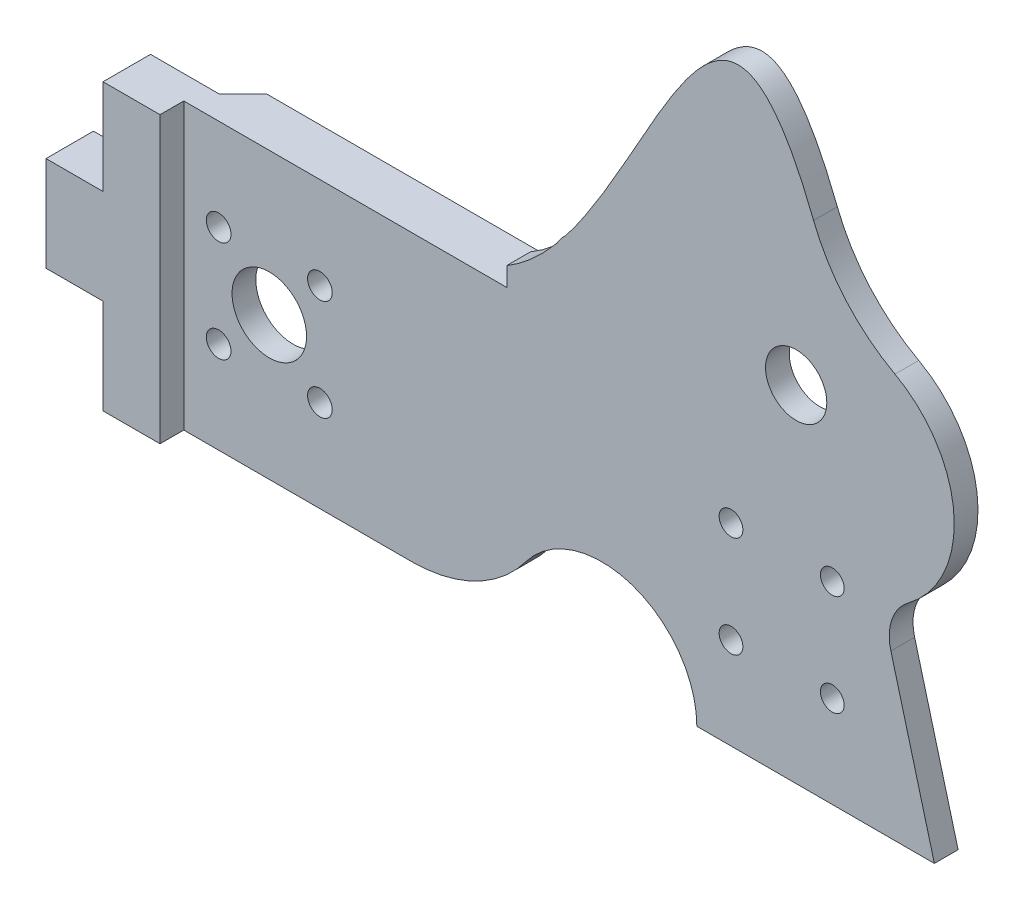
SolidWorks part; units mm, degrees
ref_plane "Front Plane" through (0, 0, 0) normal (0, 0, 1) x (1, 0, 0)
ref_plane "Top Plane" through (0, 0, 0) normal (0, 1, 0) x (1, 0, 0)
ref_plane "Right Plane" through (0, 0, 0) normal (1, 0, 0) x (0, 0, -1)
sketch "Sketch1" plane through (0, 0, 0) normal (0, 0, 1) x (1, 0, 0)
  line L0 (0, 0) -> (107.95, 0)
  line L3 (0, 38.1) -> (0, 25.4)
  line L4 (95.3675, 55.88) -> (0, 38.1)
  line L5 (0, 19.05) -> (100.2273, 19.05) construction
  line L6 (19.05, 19.05) -> (19.05, 28.62) construction
  line L7 (19.05, 19.05) -> (25.817, 25.817) construction
  line L8 (107.95, 0) -> (100.9363, 26.1756)
  line L10 (0, 12.7) -> (0, 0)
  line L11 (0, 25.4) -> (-7.62, 25.4)
  line L13 (0, 12.7) -> (-7.62, 12.7)
  line L14 (-7.62, 25.4) -> (-7.62, 12.7)
  line L15 (100.9363, 26.1756) -> (100.8688, 26.4276)
  arc A0 (100.8688, 26.4276) -> (95.3675, 55.88) centre (95.3675, 40.64) ccw
  circle A1 centre (95.3675, 40.64) radius 4.0957 construction
  circle A2 centre (19.05, 19.05) radius 9.57 construction
  circle A3 centre (25.817, 25.817) radius 1.651
  circle A4 centre (25.817, 12.283) radius 1.651
  circle A5 centre (12.283, 12.283) radius 1.651
  circle A6 centre (12.283, 25.817) radius 1.651
  point P26 (19.05, 19.05)
  dimension "D1" = 8.1915
  dimension "D5" = 15.24
  dimension "D4" = 19.14
  dimension "D7" = 3.302
  dimension "D11" = 97.0107
  dimension "D2" = 38.1
  dimension "D3" = 40.64
  dimension "D6" = 107.95
  dimension "D8" = 45
  dimension "D9" = 4
  dimension "D10" = 19.05
  dimension "D12" = 75
  dimension "D14" = 12.7
  dimension "D15" = 12.7
  dimension "D16" = 7.62
extrude "Boss-Extrude1" add sketch "Sketch1" along normal blind 3.175
sketch "Sketch2" plane through (0, 0, 3.175) normal (0, 0, 1) x (1, 0, 0)
  circle A0 centre (95.3675, 40.64) radius 38.1 construction
sketch "Sketch6" plane through (0, 0, 3.175) normal (0, 0, 1) x (1, 0, 0)
  line L0 (0, 0) -> (107.95, 0) construction
  line L1 (50.8, 0) -> (76.2, 0)
  arc A0 (76.2, 0) -> (50.8, 0) centre (63.5, 0) ccw
  dimension "D1" = 25.4
  dimension "D2" = 31.75
extrude "Cut-Extrude2" cut sketch "Sketch6" against normal blind 6.35
sketch "Sketch7" plane through (0, 0, 3.175) normal (0, 0, 1) x (1, 0, 0)
  line L0 (12.283, 25.817) -> (25.817, 12.283) construction
  line L1 (12.283, 12.283) -> (25.817, 25.817) construction
  line L2 (12.283, 25.817) -> (78.4839, 25.817) construction
  line L3 (11.7326, 12.283) -> (12.283, 12.283) construction
  circle A0 centre (19.05, 19.05) radius 4.9784
  circle A4 centre (80.7666, 12.283) radius 1.5875
  circle A5 centre (94.2997, 12.283) radius 1.5875
  circle A6 centre (80.7666, 25.817) radius 1.5875
  circle A7 centre (94.2997, 25.817) radius 1.5875
  dimension "D1" = 9.9568
  dimension "D2" = 3.175
  dimension "D3" = 13.5331
extrude "Cut-Extrude3" cut sketch "Sketch7" against normal through all
fillet "Fillet1" radius 6.35 1 edges at (100.8688, 26.4276, 1.5875)
sketch "Sketch8" plane through (0, 0, 3.175) normal (0, 0, 1) x (1, 0, 0)
  line L1 (0, 38.1) -> (50.8, 38.1)
  line L2 (0, 38.1) -> (0, 50.8)
  line L3 (0, 50.8) -> (50.8, 50.8)
  line L4 (50.8, 38.1) -> (50.8, 50.8)
  dimension "D1" = 50.8
  dimension "D2" = 12.7
extrude "Cut-Extrude4" cut sketch "Sketch8" against normal blind 50.8
sketch "Sketch9" plane through (0, 0, 3.175) normal (0, 0, 1) x (1, 0, 0)
  line L3 (50.8, 40.64) -> (57.15, 40.64)
  line L5 (57.15, 40.64) -> (50.8, 40.64)
  line L6 (57.15, 40.64) -> (57.15, 50.8)
  line L7 (57.15, 50.8) -> (50.8, 50.8)
  line L8 (50.8, 40.64) -> (50.8, 50.8)
  line L9 (0, 38.1) -> (50.8, 38.1) construction
  line M8 (50.8, 47.571) -> (50.8, 38.1)
  line M21 (95.3675, 55.88) -> (50.8, 47.571)
  dimension "D1" = 10.16
  dimension "D2" = 2.54
  dimension "D3" = 6.35
extrude "Cut-Extrude5" cut sketch "Sketch9" against normal blind 19.304 contours L3 L6 M21 M8 region at (54.0583, 44.4092, 3.175)
fillet "Fillet6" radius 6.35 1 edges at (57.15, 40.64, 1.5875)
fillet "Fillet7" radius 6.35 1 edges at (57.15, 48.7549, 1.5875)
fillet "Fillet8" radius 19.05 1 edges at (50.8, 0, 1.5875)
sketch "Sketch12" plane through (0, 0, 3.175) normal (0, 0, 1) x (1, 0, 0)
  line L0 (107.95, 0) -> (146.812, 0) construction
  line L1 (8.0257, 45.4128) -> (80.6683, 75.7903) construction
  line L2 (95.3675, 40.64) -> (80.6683, 75.7903) construction
  line L3 (80.6683, 75.7903) -> (79.4434, 78.7195) construction
  line L4 (50.8, 40.64) -> (85.0271, 40.64)
  line L5 (85.0271, 40.64) -> (95.3675, 55.88)
  arc A0 (61.8128, 49.6242) -> (56.8883, 45.1859) centre (62.9766, 43.3817) ccw construction
  circle A1 centre (19.05, 19.05) radius 28.575 construction
  circle A2 centre (95.3675, 40.64) radius 38.1 construction
  circle A3 centre (80.6683, 75.7903) radius 3.175 construction
  spline S0 degree 3 poles (50.8, 40.64) (70.7778, 52.1788) (78.5943, 111.5434) (95.3675, 55.88) knots 0 0 0 0 1 1 1 1
  dimension "D2" = 6.35
  dimension "D1" = 38.862
extrude "Boss-Extrude2" add sketch "Sketch12" against normal blind 3.175
fillet "Fillet9" radius 24.13 1 edges at (95.3675, 55.88, 1.5875)
sketch "Sketch13" plane through (0, 0, 0) normal (0, 0, -1) x (-1, 0, 0)
  line L1 (-50.8, 38.1) -> (-9.1321, 38.1)
  line L2 (-50.8, 38.1) -> (-50.8, 28.6404)
  line L3 (-50.8, 28.6404) -> (-9.1321, 28.6404)
  line L6 (-9.1321, 8.4682) -> (-38.1, 8.4682)
  line L7 (-9.1321, 8.4682) -> (-9.1321, 0)
  line L8 (-9.1321, 0) -> (-38.1, 0)
  line L9 (-38.1, 8.4682) -> (-38.1, 0)
  line L10 (-9.1321, 38.1) -> (-9.1321, 28.6404)
extrude "Boss-Extrude3" add sketch "Sketch13" along normal blind 3.175
sketch "Sketch16" plane through (0, 0, 3.175) normal (0, 0, 1) x (1, 0, 0)
  circle A0 centre (89.4737, 46.137) radius 4.0958
  circle A1 centre (94.2997, 25.817) radius 1.5875 construction
  dimension "D1" = 20.32
  dimension "D2" = 4.826
extrude "Cut-Extrude8" cut sketch "Sketch16" against normal through all
sketch "Sketch18" plane through (0, 0, 3.175) normal (0, 0, 1) x (1, 0, 0)
  line L0 (0, 0) -> (7.62, 0)
  line L1 (0, 0) -> (38.1, 0) construction
  line L2 (7.62, 0) -> (7.62, 38.1)
  line L3 (0, 38.1) -> (50.8, 38.1) construction
  line L4 (7.62, 38.1) -> (0, 38.1)
  line L5 (0, 38.1) -> (0, 25.4)
  line L6 (0, 25.4) -> (-7.62, 25.4)
  line L7 (-7.62, 25.4) -> (-7.62, 12.7)
  line L8 (-7.62, 12.7) -> (0, 12.7)
  line L9 (0, 12.7) -> (0, 0)
  dimension "D1" = 7.62
extrude "Boss-Extrude4" add sketch "Sketch18" along normal blind 3.175
sketch "Sketch19" plane through (0, 38.1, 0) normal (0, 1, 0) x (1, 0, 0)
  line L0 (9.1321, 0) -> (12.3071, 3.175)
  line L1 (9.1321, 3.175) -> (50.8, 3.175) construction
  line L2 (9.1321, 3.175) -> (9.1321, 0) construction
  line L3 (12.3071, 3.175) -> (9.1321, 3.175)
  line L4 (9.1321, 3.175) -> (9.1321, 0)
  dimension "D1" = 45
extrude "Cut-Extrude9" cut sketch "Sketch19" against normal through all
